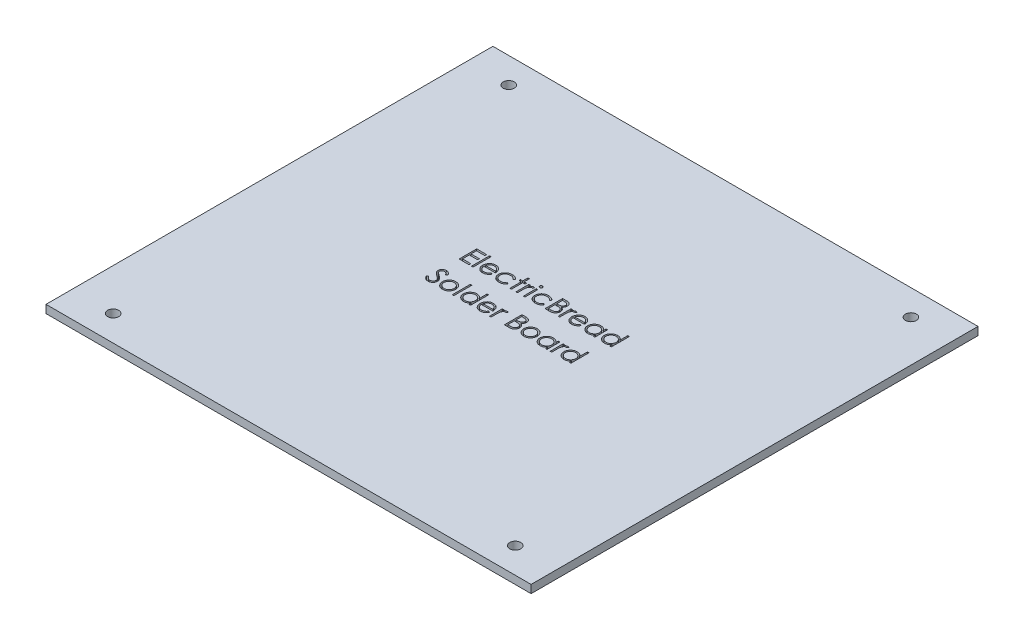
SolidWorks part; units mm, degrees
ref_plane "Front Plane" through (0, 0, 0) normal (0, 0, 1) x (1, 0, 0)
ref_plane "Top Plane" through (0, 0, 0) normal (0, 1, 0) x (1, 0, 0)
ref_plane "Right Plane" through (0, 0, 0) normal (1, 0, 0) x (0, 0, -1)
sketch "Sketch1" plane through (0, 0, 0) normal (0, 1, 0) x (1, 0, 0)
  line L1 (-48.25, -44.45) -> (48.25, -44.45)
  line L2 (-48.25, -44.45) -> (-48.25, 44.45)
  line L3 (-48.25, 44.45) -> (48.25, 44.45)
  line L4 (48.25, -44.45) -> (48.25, 44.45)
  line L5 (-48.25, -44.45) -> (48.25, 44.45) construction
  line L6 (-48.25, 44.45) -> (48.25, -44.45) construction
  point P0 (0, 0)
  dimension "D1" = 88.9
  dimension "D2" = 96.5
extrude "Boss-Extrude1" add sketch "Sketch1" along normal blind 1.6
sketch "Sketch2" plane through (0, 1.6, 0) normal (0, 1, 0) x (1, 0, 0)
  line L1 (-40, -39.35) -> (40, -39.35) construction
  line L2 (-40, -39.35) -> (-40, 39.35) construction
  line L3 (-40, 39.35) -> (40, 39.35) construction
  line L4 (40, -39.35) -> (40, 39.35) construction
  line L5 (-40, -39.35) -> (40, 39.35) construction
  line L6 (-40, 39.35) -> (40, -39.35) construction
  circle A0 centre (-40, 39.35) radius 1.1
  circle A1 centre (40, 39.35) radius 1.1
  circle A2 centre (40, -39.35) radius 1.1
  circle A3 centre (-40, -39.35) radius 1.1
  text T0 "ElectricBread\r\nSolder Board"
  point P0 (0, 0)
  dimension "D3" = 2.2
  dimension "D1" = 80
  dimension "D2" = 78.7
extrude "Cut-Extrude1" cut sketch "Sketch2" against normal up to surface (1.6 mm away) up to face at (0, 0, 0)
